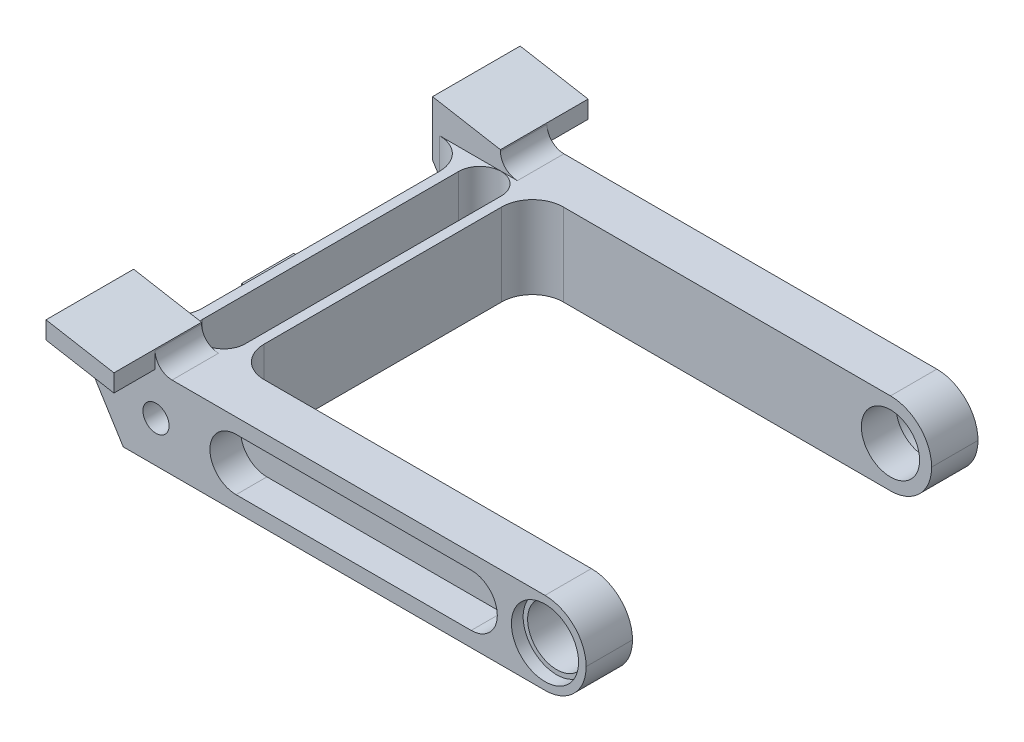
SolidWorks part; units mm, degrees
ref_plane "Front Plane" through (0, 0, 0) normal (0, 0, 1) x (1, 0, 0)
ref_plane "Top Plane" through (0, 0, 0) normal (0, 1, 0) x (1, 0, 0)
ref_plane "Right Plane" through (0, 0, 0) normal (1, 0, 0) x (0, 0, -1)
sketch "Sketch1" plane through (0, 0, 0) normal (0, 1, 0) x (1, 0, 0)
  line L0 (0, 11.5316) -> (0, -11.5316)
  line L1 (-2.9972, -14.5288) -> (-3.683, -14.5288)
  line L2 (-3.683, -14.5288) -> (-3.683, -23.0505)
  line L3 (-3.683, -23.0505) -> (2.921, -23.0505)
  line L4 (2.921, -23.0505) -> (2.921, -19.05)
  line L5 (2.921, -19.05) -> (44.831, -19.05)
  line L6 (44.831, -19.05) -> (44.831, -14.5415)
  line L7 (44.831, -14.5415) -> (9.017, -14.5415)
  line L8 (6.0198, -11.5443) -> (6.0198, 11.5443)
  line L9 (9.017, 14.5415) -> (44.831, 14.5415)
  line L10 (44.831, 14.5415) -> (44.831, 19.05)
  line L11 (44.831, 19.05) -> (2.921, 19.05)
  line L12 (2.921, 19.05) -> (2.921, 23.0505)
  line L13 (2.921, 23.0505) -> (-3.683, 23.0505)
  line L14 (-3.683, 23.0505) -> (-3.683, 14.5288)
  line L15 (-3.683, 14.5288) -> (-2.9972, 14.5288)
  arc A0 (-2.9972, 14.5288) -> (0, 11.5316) centre (-2.9972, 11.5316) cw
  arc A1 (0, -11.5316) -> (-2.9972, -14.5288) centre (-2.9972, -11.5316) cw
  arc A2 (9.017, -14.5415) -> (6.0198, -11.5443) centre (9.017, -11.5443) cw
  arc A3 (6.0198, 11.5443) -> (9.017, 14.5415) centre (9.017, 11.5443) cw
  point P23 (6.0198, -14.5415)
  point P26 (6.0198, 14.5415)
  dimension "D13" = 2.9972
  dimension "D1" = 46.101
  dimension "D2" = 48.514
  dimension "D3" = 29.0576
  dimension "D4" = 14.5288
  dimension "D5" = 23.0505
  dimension "D6" = 3.683
  dimension "D7" = 6.604
  dimension "D8" = 38.1
  dimension "D9" = 19.05
  dimension "D10" = 6.0198
  dimension "D11" = 29.083
  dimension "D12" = 14.5415
extrude "Boss-Extrude1" add sketch "Sketch1" along normal blind 10.9474
sketch "Sketch2" plane through (0, 0, 23.0505) normal (0, 0, 1) x (1, 0, 0)
  line L0 (-0.1754, 0) -> (-3.683, 5.6134)
  line L1 (-3.683, 10.9474) -> (-3.683, 0) construction
  line L2 (-3.683, 5.6134) -> (-3.683, 0)
  line L3 (-3.683, 0) -> (2.921, 0) construction
  line L4 (-3.683, 0) -> (-0.1754, 0)
  line L5 (2.921, 0) -> (44.831, 0) construction
  line L6 (-3.683, 10.9474) -> (2.921, 10.9474) construction
  dimension "D1" = 58
  dimension "D2" = 5.334
extrude "Cut-Extrude1" cut sketch "Sketch2" against normal through all
sketch "Sketch3" plane through (0, 0, 19.05) normal (0, 0, 1) x (1, 0, 0)
  line L0 (4.572, 8.001) -> (44.831, 8.001)
  line L1 (2.921, 0) -> (44.831, 0) construction
  line L2 (2.921, 10.9474) -> (2.921, 0) construction
  line L3 (2.921, 10.9474) -> (2.921, 9.652)
  line L4 (2.921, 10.9474) -> (44.831, 10.9474) construction
  line L5 (44.831, 10.9474) -> (44.831, 0) construction
  line L6 (2.921, 10.9474) -> (44.831, 10.9474)
  line L7 (44.831, 10.9474) -> (44.831, 8.001)
  arc A0 (4.572, 8.001) -> (2.921, 9.652) centre (4.572, 9.652) cw
  dimension "D2" = 1.651
  dimension "D1" = 8.001
extrude "Cut-Extrude2" cut sketch "Sketch3" against normal through all
sketch "Sketch4" plane through (6.0198, 0, 0) normal (1, 0, 0) x (0, 0, -1)
  line L0 (-14.5288, 10.9474) -> (-14.5288, 4.5159) construction
  line L1 (-14.5288, 10.9474) -> (-14.5288, 8.001)
  line L2 (11.5443, 8.001) -> (-11.5443, 8.001) construction
  line L3 (14.5288, 10.9474) -> (14.5288, 4.5159) construction
  line L4 (-23.0505, 10.9474) -> (23.0505, 10.9474) construction
  line L5 (14.5288, 8.001) -> (-14.5288, 8.001)
  line L6 (14.5288, 10.9474) -> (14.5288, 8.001)
  line L7 (-14.5288, 10.9474) -> (14.5288, 10.9474)
extrude "Cut-Extrude3" cut sketch "Sketch4" against normal blind 10.9474
sketch "Sketch5" plane through (0, 8.001, 0) normal (0, 1, 0) x (1, 0, 0)
  line L0 (0, 0) -> (6.0198, 0) construction
  line L1 (6.0198, 11.5443) -> (6.0198, -11.5443) construction
  line L2 (3.0099, 0) -> (3.0099, -11.4067) construction
  line L3 (3.0099, -12.446) -> (3.0099, 12.446) construction
  line L4 (0.9398, -12.446) -> (0.9398, 12.446)
  line L5 (5.08, -12.446) -> (5.08, 12.446)
  arc A0 (0.9398, -12.446) -> (5.08, -12.446) centre (3.0099, -12.446) ccw
  arc A1 (5.08, 12.446) -> (0.9398, 12.446) centre (3.0099, 12.446) ccw
  point P9 (3.0099, 0)
  dimension "D1" = 2.0701
  dimension "D2" = 12.446
  dimension "D3" = 12.446
extrude "Cut-Extrude4" cut sketch "Sketch5" against normal blind 6.5278
fillet "Fillet1" radius 4.0005 4 edges at (44.831, 8.001, -16.7958) (44.831, 0, -16.7958) (44.831, 0, 16.7957) (44.831, 8.001, 16.7957)
sketch "Sketch6" plane through (0, 0, 23.0505) normal (0, 0, 1) x (1, 0, 0)
  line L0 (-3.683, 10.9474) -> (2.921, 9.7829)
  line L1 (-3.683, 10.9474) -> (2.921, 10.9474) construction
  line L2 (2.921, 10.9474) -> (2.921, 0) construction
  line L3 (-3.683, 10.9474) -> (2.921, 10.9474)
  line L4 (2.921, 10.9474) -> (2.921, 9.7829)
  dimension "D1" = 10
extrude "Cut-Extrude5" cut sketch "Sketch6" against normal through all
sketch "Sketch7" plane through (0, 0, 23.0505) normal (0, 0, 1) x (1, 0, 0)
  line L0 (-3.683, 10.9474) -> (2.921, 9.7829) construction
  line L1 (-3.683, 10.9474) -> (2.921, 9.7829) construction
  line L2 (-3.683, 10.9474) -> (-3.683, 5.6134) construction
  line L3 (2.921, 9.7829) -> (2.921, 0) construction
  line L4 (-0.1754, 0) -> (-3.683, 5.6134) construction
  line L5 (-0.1754, 0) -> (2.921, 0) construction
  line L6 (-3.683, 8.9872) -> (-3.683, 5.6134)
  line L7 (2.921, 7.8228) -> (2.921, 0)
  line L8 (-0.1754, 0) -> (-3.683, 5.6134)
  line L9 (-0.1754, 0) -> (2.921, 0)
  line L10 (-3.683, 8.9872) -> (2.921, 7.8228)
  line L11 (-4.0182, 9.0463) -> (2.5858, 7.8819) construction
  dimension "D1" = 1.9304
extrude "Cut-Extrude6" cut sketch "Sketch7" against normal up to surface (4.0005 mm away) up to face at (23.0369, 4.8854, 19.05)
sketch "Sketch8" plane through (0, 0, -23.0505) normal (0, 0, -1) x (-1, 0, 0)
  line L0 (3.683, 8.9872) -> (-2.921, 7.8228)
  line L1 (4.0182, 9.0463) -> (-2.5858, 7.8819) construction
  line L5 (3.683, 5.6134) -> (3.683, 10.9474)
  line L6 (3.683, 10.9474) -> (-2.921, 9.7829)
  line L7 (-2.921, 9.7829) -> (-2.921, 0)
  line L8 (-2.921, 0) -> (0.1754, 0)
  line L9 (0.1754, 0) -> (3.683, 5.6134)
  line L10 (3.683, 5.6134) -> (3.683, 8.9872)
  line L11 (3.683, 10.9474) -> (-2.921, 9.7829) construction
  line L12 (-2.921, 7.8228) -> (-2.921, 0)
  line L13 (-2.921, 0) -> (0.1754, 0)
  line L14 (0.1754, 0) -> (3.683, 5.6134)
  dimension "D1" = 0
  dimension "D2" = 1.9304
extrude "Cut-Extrude7" cut sketch "Sketch8" against normal up to surface (4.0005 mm away) up to face at (23.0369, 4.8854, -19.05)
sketch "Sketch9" plane through (0, 0, -19.05) normal (0, 0, -1) x (-1, 0, 0)
  circle A0 centre (-40.8305, 4.0005) radius 2.8321
  dimension "D1" = 5.6642
extrude "Cut-Extrude8" cut sketch "Sketch9" against normal through all
sketch "Sketch10" plane through (0, 0, -19.05) normal (0, 0, -1) x (-1, 0, 0)
  circle A0 centre (-40.8305, 4.0005) radius 3.2639
  dimension "D1" = 6.5278
extrude "Cut-Extrude9" cut sketch "Sketch10" against normal blind 1.143
sketch "Sketch11" plane through (0, 0, 19.05) normal (0, 0, 1) x (1, 0, 0)
  circle A0 centre (40.8305, 4.0005) radius 3.2639
  dimension "D1" = 6.5278
extrude "Cut-Extrude10" cut sketch "Sketch11" against normal blind 1.143
sketch "Sketch12" plane through (0, 0, 19.05) normal (0, 0, 1) x (1, 0, 0)
  line L0 (37.5666, 4.0005) -> (37.5666, 7.2644) construction
  line L1 (33.655, 4.0005) -> (33.655, 7.2644) construction
  line L2 (33.655, 4.0005) -> (10.795, 4.0005) construction
  line L3 (33.655, 1.4605) -> (10.795, 1.4605)
  line L4 (33.655, 6.5405) -> (10.795, 6.5405)
  circle A0 centre (40.8305, 4.0005) radius 3.2639 construction
  arc A1 (33.655, 1.4605) -> (33.655, 6.5405) centre (33.655, 4.0005) ccw
  arc A2 (10.795, 6.5405) -> (10.795, 1.4605) centre (10.795, 4.0005) ccw
  point P6 (22.225, 4.0005)
  dimension "D2" = 2.54
  dimension "D3" = 22.86
  dimension "D1" = 3.9116
extrude "Cut-Extrude11" cut sketch "Sketch12" against normal blind 2.9972
sketch "Sketch13" plane through (0, 0, -19.05) normal (0, 0, -1) x (-1, 0, 0)
  line L0 (-33.655, 6.5405) -> (-10.795, 6.5405) construction
  line L1 (-10.795, 1.4605) -> (-33.655, 1.4605) construction
  line L2 (-33.655, 6.5405) -> (-10.795, 6.5405)
  line L3 (-10.795, 1.4605) -> (-33.655, 1.4605)
  arc A0 (-33.655, 6.5405) -> (-33.655, 1.4605) centre (-33.655, 4.0005) ccw construction
  arc A1 (-10.795, 1.4605) -> (-10.795, 6.5405) centre (-10.795, 4.0005) ccw construction
  arc A2 (-33.655, 6.5405) -> (-33.655, 1.4605) centre (-33.655, 4.0005) ccw
  arc A3 (-10.795, 1.4605) -> (-10.795, 6.5405) centre (-10.795, 4.0005) ccw
extrude "Cut-Extrude13" cut sketch "Sketch13" against normal blind 2.9972
sketch "Sketch14" plane through (0, 0, -19.05) normal (0, 0, -1) x (-1, 0, 0)
  line L0 (-40.8305, 4.0005) -> (-40.8305, -1.6991) construction
  line L1 (-0.9398, 1.4732) -> (-5.08, 1.4732) construction
  circle A0 centre (-3.0099, 4.0005) radius 1.27
  point P5 (-3.0099, 1.4732)
  dimension "D1" = 2.54
  dimension "D2" = 0
extrude "Cut-Extrude14" cut sketch "Sketch14" against normal through all
sketch "Sketch15" plane through (0, 0, 0) normal (0, -1, 0) x (1, 0, 0)
  line L2 (-5.1816, -2.54) -> (-5.1816, 2.54)
  line L3 (0, 0) -> (-5.1816, 0) construction
  line L4 (-2.5, 2.54) -> (-5.1816, 2.54)
  line L5 (-2.5, -2.54) -> (-5.1816, -2.54)
  line L7 (0, -5.04) -> (0, 5.04)
  line L8 (0, 2.54) -> (-5.1816, 2.54) construction
  arc A0 (0, -5.04) -> (-2.5, -2.54) centre (-2.5, -5.04) ccw
  arc A1 (0, 5.04) -> (-2.5, 2.54) centre (-2.5, 5.04) cw
  circle A2 centre (-3.6577, 0) radius 0.8382
  point P0 (0, -11.5316)
  point P1 (0, 11.5316)
  dimension "D3" = 2.5
  dimension "D4" = 1.6764
  dimension "D2" = 2.54
extrude "Boss-Extrude2" add sketch "Sketch15" against normal blind 2.9972
sketch "Sketch16" plane through (0, 0, 19.05) normal (0, 0, 1) x (1, 0, 0)
  line L0 (2.921, 7.8228) -> (-3.683, 8.9872) construction
  line L1 (2.921, 7.8228) -> (-3.683, 8.9872)
  line L2 (-3.683, 9.2429) -> (2.921, 8.0784)
  line L3 (-3.683, 10.9474) -> (-3.683, 8.9872) construction
  line L4 (-3.683, 9.2429) -> (-3.683, 8.9872)
  line L5 (2.921, 9.7829) -> (2.921, 7.8228) construction
  line L6 (2.921, 8.0784) -> (2.921, 7.8228)
  circle A0 centre (3.0099, 4.0005) radius 4.0005 construction
  dimension "D1" = 8.001
extrude "Cut-Extrude15" cut sketch "Sketch16" along normal up to surface (4.0005 mm away) up to face at (-0.381, 9.3851, 23.0505)
sketch "Sketch17" plane through (0, 0, -19.05) normal (0, 0, -1) x (-1, 0, 0)
  line L0 (-2.921, 8.0784) -> (3.683, 9.2429) construction
  line L1 (3.683, 8.9872) -> (-2.921, 7.8228) construction
  line L2 (-2.921, 9.7829) -> (-2.921, 7.8228) construction
  line L3 (3.683, 10.9474) -> (3.683, 8.9872) construction
  line L4 (-2.921, 8.0784) -> (3.683, 9.2429)
  line L5 (3.683, 8.9872) -> (-2.921, 7.8228)
  line L6 (-2.921, 8.0784) -> (-2.921, 7.8228)
  line L7 (3.683, 9.2429) -> (3.683, 8.9872)
extrude "Cut-Extrude16" cut sketch "Sketch17" along normal up to surface (4.0005 mm away) up to face at (-0.381, 9.3851, -23.0505)
scale "Scale1" scale about centroid uniform scaling yes scale factor 0.6
